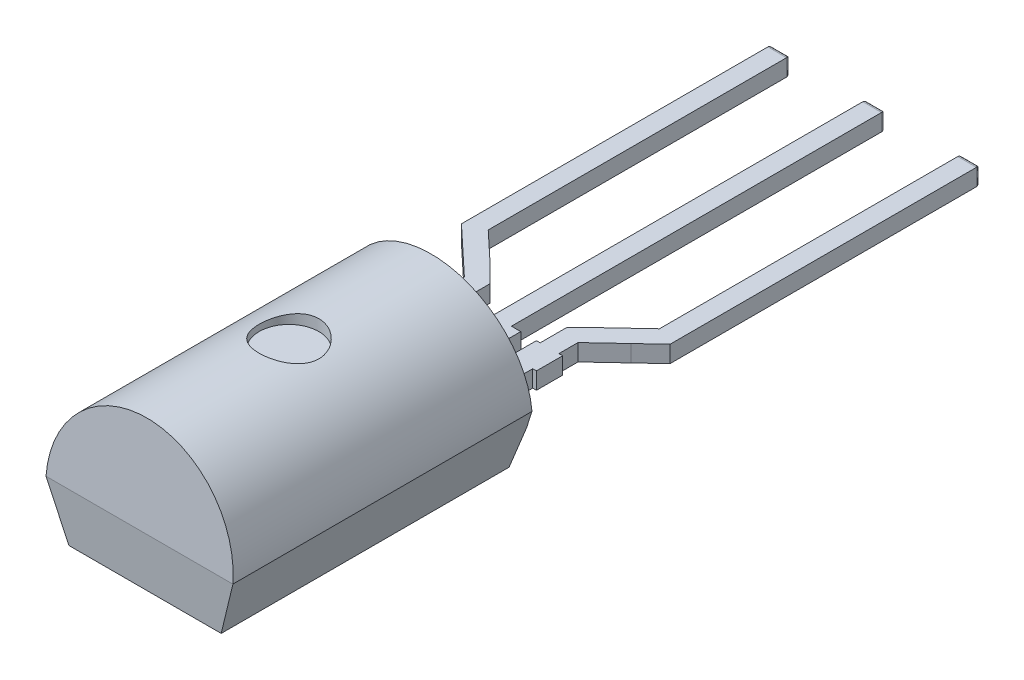
SolidWorks part; units mm, degrees
ref_plane "Front Plane" through (0, 0, 0) normal (0, 0, 1) x (1, 0, 0)
ref_plane "Top Plane" through (0, 0, 0) normal (0, 1, 0) x (1, 0, 0)
ref_plane "Right Plane" through (0, 0, 0) normal (1, 0, 0) x (0, 0, -1)
sketch "Sketch1" plane through (0, 0, 0) normal (0, 0, 1) x (1, 0, 0)
  line L4 (-2.0365, -1.45) -> (2.0365, -1.45)
  line L5 (-2.5, 0) -> (-2.0365, -1.45)
  line L6 (2.0365, -1.45) -> (2.5, 0)
  arc A1 (2.5, 0) -> (-2.5, 0) centre (0, 0) ccw
  dimension "D1" = 5
sketch3d "3DSketch4" plane through (0, 0, 0) normal (0, 0, 1) x (1, 0, 0)
extrude "Boss-Extrude2" add sketch "Sketch1" along normal blind 8
sketch "Sketch2" plane through (0, 0, 0) normal (0, 0, -1) x (-1, 0, 0)
  line L0 (-0.4, 0) -> (0.4, 0)
  line L3 (-0.4, -0.45) -> (0.4, -0.45)
  line L4 (-0.4, -0.45) -> (-0.4, 0)
  line L6 (0.4, -0.45) -> (0.4, 0)
  point P7 (0, -0.225)
  dimension "D2" = 0.8
ref_plane "Plane1" through (0, -0.225, 0) normal (0, 1, 0) x (1, 0, 0)
sketch "Sketch3" plane through (0, -0.225, 0) normal (0, 1, 0) x (1, 0, 0)
  line L0 (0.4, 0) -> (-0.4, 0) construction
  line L1 (-0.4, 0) -> (0.4, 0)
  line L2 (-0.4, 0) -> (-0.4, 1)
  line L4 (0.4, 0) -> (0.4, 1)
  line L6 (0.25, 1.7) -> (0.5, 1.7)
  line L7 (-0.5, 1.7) -> (-0.25, 1.7)
  line L8 (-0.5, 1.7) -> (-0.5, 1)
  line L9 (-0.5, 1) -> (-0.4, 1)
  line L10 (0.5, 1.7) -> (0.5, 1)
  line L11 (0.4, 1) -> (0.5, 1)
  line L14 (-0.25, 11.7) -> (0.25, 11.7)
  line L15 (-0.25, 11.7) -> (-0.25, 1.7)
  line L17 (0.25, 11.7) -> (0.25, 1.7)
  dimension "D1" = 1
  dimension "D3" = 1
  dimension "D4" = 0.5
  dimension "D5" = 10
extrude "Boss-Extrude3" add sketch "Sketch3" along normal blind 0.225 contours L2 L9 L8 L7 L15 L14 L17 L6 L10 L11 L4 L1
extrude "Boss-Extrude4" add sketch "Sketch3<3>" against normal blind 0.225
sketch "Sketch3<3>" plane through (0, -0.225, 0) normal (0, 1, 0) x (1, 0, 0) same geometry as "Sketch3"
sketch "Sketch7" plane through (0, -0.225, 0) normal (0, 1, 0) x (1, 0, 0)
  line L0 (0, 0) -> (1.27, 0)
  line L1 (-2.0365, 0) -> (2.0365, 0) construction
  line L2 (1.02, 0) -> (1.52, 0)
  line L4 (1.02, 0) -> (1.02, 1)
  line L6 (1.52, 0) -> (1.52, 1)
  line L8 (0.92, 1.7) -> (1.02, 1.7)
  line L9 (0.92, 1.7) -> (0.92, 1)
  line L13 (0.92, 1) -> (1.02, 1)
  line L14 (1.62, 1) -> (1.62, 1.7)
  line L15 (1.02, 1.7) -> (1.02, 2.3975)
  line L18 (1.52, 1) -> (1.62, 1)
  line L19 (1.52, 1.7) -> (1.62, 1.7)
  line L20 (0, 0) -> (2.54, 0)
  line L21 (1.52, 2.212) -> (2.79, 3.4033)
  line L22 (2.54, 0) -> (2.79, 0)
  line L23 (2.29, -11.7) -> (2.79, -11.7)
  line L24 (2.29, 2.8975) -> (2.29, 2.9343)
  line L25 (2.29, 11.7) -> (2.79, 11.7)
  line L26 (2.79, 3.4033) -> (2.79, 11.7)
  line L30 (2.79, 4.0889) -> (2.79, 3.4033)
  line L32 (1.02, 2.3975) -> (1.02, 2.212)
  line L35 (1.52, 2.8975) -> (2.29, 3.6198)
  line L36 (2.2494, 2.8975) -> (2.2501, 2.8968)
  line L37 (2.29, 3.6198) -> (2.29, 11.7)
  line L38 (2.2494, 2.8975) -> (2.29, 2.8975)
  line L39 (1.52, 2.8975) -> (1.02, 2.3975)
  line L40 (1.52, 2.212) -> (1.52, 1.7)
  point P6 (1.27, 1)
  point P15 (0, 0)
  dimension "D1" = 1.27
  dimension "D2" = 0.5
  dimension "D3" = 1
  dimension "D4" = 0.7
  dimension "D5" = 0.7
  dimension "D7" = 2.54
  dimension "D8" = 0.5
extrude "Boss-Extrude7" add sketch "Sketch7" along normal blind 0.225 contours L40 L21 L36 L38 L26 L25 L37 L35 L39 L15 L8 L9 L13 L4 L0 L2 L6 L18 L14 L19 region at (1.1385, -0.225, -0.5)
extrude "Boss-Extrude8" add sketch "Sketch7<7>" against normal blind 0.225 contours L40 L21 L36 L38 L26 L25 L37 L35 L39 L15 L8 L9 L13 L4 L0 L2 L6 L18 L14 L19 region at (1.1385, -0.225, -0.5)
sketch "Sketch7<7>" plane through (0, -0.225, 0) normal (0, 1, 0) x (1, 0, 0) same geometry as "Sketch7"
mirror "Mirror2" about plane through (0, 0, 0) normal (1, 0, 0) of "Boss-Extrude7", "Boss-Extrude8"
ref_plane "Plane3" through (2.5, 0, 0) normal (1, 0, 0) x (0, 0, -1)
sketch "Sketch9" plane through (2.5, 0, 0) normal (1, 0, 0) x (0, 0, -1)
  line L0 (-8, 0) -> (-7.8, 2.5)
  line L2 (-8, 0) -> (-8, 2.5)
  line L3 (-8, 2.5) -> (-7.8, 2.5)
  dimension "D1" = 0.2
extrude "Cut-Extrude1" cut sketch "Sketch9" against normal blind 5
sketch "Sketch10" plane through (2.5, 0, 0) normal (1, 0, 0) x (0, 0, -1)
  line L0 (-8, -1.45) -> (0, -1.45) construction
  line L2 (-8, 0) -> (-8, -1.45)
  line L3 (-8, -1.45) -> (-7.85, -1.45)
  line L5 (-8, 0) -> (-7.85, -1.45)
  dimension "D1" = 0.15
extrude "Cut-Extrude2" cut sketch "Sketch10" against normal blind 5
sketch "Sketch11" plane through (2.5, 0, 0) normal (1, 0, 0) x (0, 0, -1)
  line L0 (-0.2, 2.5) -> (0, 0)
  line L2 (0, 0) -> (0, 2.5)
  line L3 (0, 2.5) -> (-0.2, 2.5)
  dimension "D1" = 2.5
  dimension "D2" = 0.2
extrude "Cut-Extrude3" cut sketch "Sketch11" against normal blind 5
sketch "Sketch12" plane through (2.5, 0, 0) normal (1, 0, 0) x (0, 0, -1)
  line L0 (-7.85, -1.45) -> (0, -1.45) construction
  line L2 (0, -0.45) -> (0, -1.45)
  line L3 (0, -1.45) -> (-0.15, -1.45)
  line L7 (0, -0.45) -> (-0.15, -1.45)
  dimension "D1" = 0.15
extrude "Cut-Extrude7" cut sketch "Sketch12" against normal blind 5
fillet "Fillet2" radius 0.1 12 edges at (2.54, 0, -11.7) (2.29, -0.225, -11.7) (2.54, -0.45, -11.7) (2.79, -0.225, -11.7) (-2.54, 0, -11.7) (-2.79, -0.225, -11.7) (-2.54, -0.45, -11.7) (-2.29, -0.225, -11.7) (0, -0.45, -11.7) (0.25, -0.225, -11.7) (-0.25, -0.225, -11.7) (0, 0, -11.7)
ref_plane "Plane4" through (0, 2.5, 0) normal (0, 1, 0) x (1, 0, 0)
sketch "Sketch13" plane through (0, 2.5, 0) normal (0, 1, 0) x (1, 0, 0)
  circle A0 centre (0, -4) radius 0.8
  dimension "D1" = 1.6
extrude "Cut-Extrude8" cut sketch "Sketch13" against normal blind 0.3
